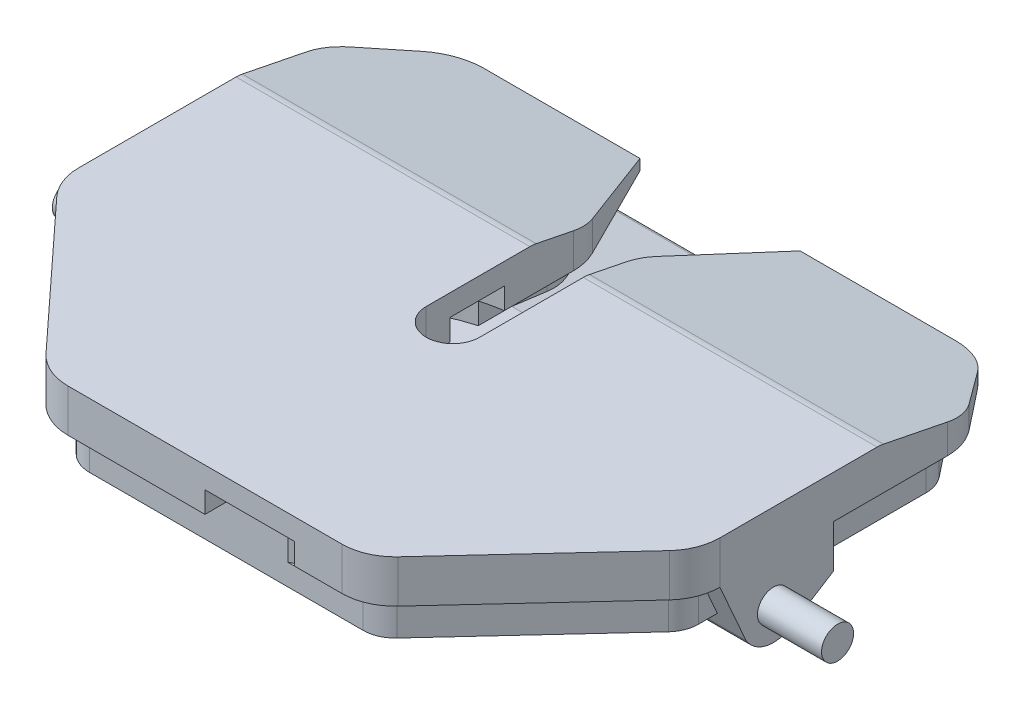
SolidWorks part; units mm, degrees
note: The reader was unsure of these and kept them because the rebuilt part matched: shared geometry of "Sketch1<4>", "Sketch4<3>".
ref_plane "Front Plane" through (0, 0, 0) normal (0, 0, 1) x (1, 0, 0)
ref_plane "Top Plane" through (0, 0, 0) normal (0, 1, 0) x (1, 0, 0)
ref_plane "Right Plane" through (0, 0, 0) normal (1, 0, 0) x (0, 0, -1)
sketch "Sketch1" plane through (0, 0, 0) normal (0, 1, 0) x (1, 0, 0)
  line L0 (-25, 0) -> (-25, 137.7264)
  line L1 (-30.4844, 160.9801) -> (-74.949, 250)
  line L2 (-74.949, 250) -> (-220.7208, 250)
  line L3 (0, 0) -> (0, 250.2014) construction
  line L4 (-45, 0) -> (-45, 133.0094)
  line L5 (-50.4844, 156.263) -> (-97.3051, 250)
  line L6 (-45, 145.283) -> (-92.8412, 241.063) construction
  line L7 (50.4844, 156.263) -> (97.3051, 250)
  line L8 (45, 0) -> (45, 133.0094)
  line L9 (74.949, 250) -> (220.7208, 250)
  line L10 (30.4844, 160.9801) -> (74.949, 250)
  line L11 (25, 0) -> (25, 137.7264)
  line L12 (-128.1169, -232.1298) -> (128.1169, -232.1298)
  line L13 (0, 0) -> (0, -232.1298) construction
  line L14 (-164.8474, -216.0543) -> (-286.7305, -84.0895)
  line L15 (-300, -50.1651) -> (-300, 162.9177)
  line L16 (-289.2422, 193.9023) -> (-259.963, 230.9846)
  line L17 (289.2422, 193.9023) -> (259.963, 230.9846)
  line L18 (300, -50.1651) -> (300, 162.9177)
  line L19 (164.8474, -216.0543) -> (286.7305, -84.0895)
  line L20 (-45, 0) -> (-45, 145.283) construction
  line L21 (-25, 0) -> (-25, 150) construction
  line L22 (-25, 150) -> (-74.949, 250) construction
  line L23 (244.2661, 218.5908) -> (220.7208, 250)
  line L24 (-273.5453, 181.5085) -> (-244.2661, 218.5908)
  line L25 (-280, -50.1651) -> (-280, 162.9177)
  line L26 (-150.1552, -202.4845) -> (-272.0383, -70.5197)
  line L27 (-128.1169, -212.1298) -> (128.1169, -212.1298)
  line L28 (150.1552, -202.4845) -> (272.0383, -70.5197)
  line L29 (280, -50.1651) -> (280, 162.9177)
  line L30 (273.5453, 181.5085) -> (244.2661, 218.5908)
  line L36 (-244.2661, 218.5908) -> (-220.7208, 250)
  line L38 (-87.3153, 230) -> (-220.7208, 230) construction
  line L39 (-48.3766, 152.0431) -> (-87.3153, 230) construction
  line L40 (-45, 0) -> (-45, 137.7264) construction
  line L41 (48.3766, 152.0431) -> (87.3153, 230) construction
  line L42 (45, 0) -> (45, 137.7264) construction
  line L43 (87.3153, 230) -> (220.7208, 230) construction
  arc A1 (-25, 0) -> (25, 0) centre (0, 0) ccw
  arc A2 (-220.7208, 250) -> (-259.963, 230.9846) centre (-220.7208, 200) ccw
  arc A3 (220.7208, 250) -> (259.963, 230.9846) centre (220.7208, 200) cw
  arc A4 (289.2422, 193.9023) -> (300, 162.9177) centre (250, 162.9177) cw
  arc A5 (300, -50.1651) -> (286.7305, -84.0895) centre (250, -50.1651) cw
  arc A6 (128.1169, -232.1298) -> (164.8474, -216.0543) centre (128.1169, -182.1298) ccw
  arc A7 (-128.1169, -232.1298) -> (-164.8474, -216.0543) centre (-128.1169, -182.1298) cw
  arc A8 (-286.7305, -84.0895) -> (-300, -50.1651) centre (-250, -50.1651) cw
  arc A9 (-300, 162.9177) -> (-289.2422, 193.9023) centre (-250, 162.9177) cw
  arc A10 (45, 133.0094) -> (50.4844, 156.263) centre (97.0392, 133.0094) cw
  arc A11 (25, 137.7264) -> (30.4844, 160.9801) centre (77.0392, 137.7264) cw
  arc A12 (-45, 133.0094) -> (-50.4844, 156.263) centre (-97.0392, 133.0094) ccw
  arc A13 (-25, 137.7264) -> (-30.4844, 160.9801) centre (-77.0392, 137.7264) ccw
  arc A15 (-280, 162.9177) -> (-273.5453, 181.5085) centre (-250, 162.9177) cw
  arc A16 (-272.0383, -70.5197) -> (-280, -50.1651) centre (-250, -50.1651) cw
  arc A17 (-128.1169, -212.1298) -> (-150.1552, -202.4845) centre (-128.1169, -182.1298) cw
  arc A18 (128.1169, -212.1298) -> (150.1552, -202.4845) centre (128.1169, -182.1298) ccw
  arc A19 (280, -50.1651) -> (272.0383, -70.5197) centre (250, -50.1651) cw
  arc A20 (273.5453, 181.5085) -> (280, 162.9177) centre (250, 162.9177) cw
  arc A23 (-45, 0) -> (45, 0) centre (0, 0) ccw
  arc A25 (-220.7208, 230) -> (-244.2661, 218.5908) centre (-220.7208, 200) ccw construction
  arc A26 (-45, 137.7264) -> (-48.3766, 152.0431) centre (-77.0392, 137.7264) ccw construction
  arc A27 (45, 137.7264) -> (48.3766, 152.0431) centre (77.0392, 137.7264) cw construction
  arc A28 (220.7208, 230) -> (244.2661, 218.5908) centre (220.7208, 200) cw construction
  point P29 (-244.949, 250)
  point P32 (244.949, 250)
  point P35 (300, 180.2776)
  point P38 (300, -69.7224)
  point P41 (150, -232.1298)
  point P44 (-150, -232.1298)
  point P47 (-300, -69.7224)
  point P50 (-300, 180.2776)
  point P53 (45, 145.283)
  point P56 (25, 150)
  point P63 (-25, 150)
  dimension "D1" = 50
  dimension "D3" = 50
  dimension "D12" = 52.0392
  dimension "D4" = 150
  dimension "D5" = 100
  dimension "D6" = 20
  dimension "D7" = 170
  dimension "D8" = 300
  dimension "D9" = 250
  dimension "D10" = 232.1298
  dimension "D11" = 300
  dimension "D13" = 20
extrude "Boss-Extrude1" add sketch "Sketch1" along normal blind 40
extrude "Boss-Extrude2" add sketch "Sketch1<4>" against normal blind 40 contours A23 L4 A12 L5 L2 L36 L24 A15 L25 A16 L26 A17 L27 A18 L28 A19 L29 A20 L30 L23 L9 L7 A10 L8
sketch "Sketch1<4>" plane through (0, 0, 0) normal (0, 1, 0) x (1, 0, 0) same geometry as "Sketch1"
sketch "Sketch2" plane through (0, 0, 0) normal (1, 0, 0) x (0, 0, -1)
  line L0 (100, 40) -> (250, 10)
  line L1 (-50.1651, 40) -> (162.9177, 40) construction
  line L3 (100, 40) -> (250, 40)
  line L4 (250, 40) -> (250, 10)
  dimension "D1" = 100
  dimension "D2" = 30
extrude "Cut-Extrude1" cut sketch "Sketch2" against normal mid plane 680
fillet "Fillet1" radius 30 2 edges at (-162.5, 40, -100) (162.5, 40, -100)
sketch "Sketch3" plane through (0, 0, 0) normal (1, 0, 0) x (0, 0, -1)
  line L0 (-181.9227, -20) -> (100, -20)
  line L1 (100, -20) -> (250, -40)
  line L2 (-50.1651, -40) -> (162.9177, -40) construction
  line L3 (-181.9227, -20) -> (-181.9227, -40)
  line L4 (-202.4845, -40) -> (-70.5197, -40) construction
  line L5 (-181.9227, -40) -> (-50.1651, -40)
  line L6 (250, -40) -> (250, -50)
  line L7 (250, -50) -> (-50.1651, -50)
  line L8 (-50.1651, -50) -> (-50.1651, -40)
  dimension "D1" = 100
  dimension "D2" = 20
  dimension "D3" = 10
extrude "Boss-Extrude3" add sketch "Sketch3" along normal mid plane 330
fillet "Fillet2" radius 5 1 edges at (0, -40, -250)
sketch "Sketch4" plane through (280, 0, 0) normal (1, 0, 0) x (0, 0, -1)
  line L0 (-50.1651, -40) -> (250, -40) construction
  line L1 (15.9641, -65.3997) -> (56.3763, -40)
  line L2 (-50.1651, -40) -> (162.9177, -40) construction
  line L3 (56.3763, -40) -> (56.3763, 0)
  line L4 (-50.1651, 0) -> (162.9177, 0) construction
  line L5 (56.3763, 0) -> (-50.1651, 0)
  line L6 (-50.1651, 0) -> (-25.6227, -55.6038)
  arc A0 (-28.7955, -48.4153) -> (15.9641, -65.3997) centre (0, -40) ccw
  circle A1 centre (0, -40) radius 15
  line M1 (162.9177, 0) -> (-50.1651, 0)
  line M3 (-50.1651, -40) -> (162.9177, -40)
  dimension "D1" = 30
  dimension "D2" = 60
extrude "Boss-Extrude4" add sketch "Sketch4" along normal blind 20 and the other way blind 80 contours A1 L3 L6 M3 M1 | A1 L6 A0 L1 M3
extrude "Boss-Extrude5" add sketch "Sketch4<3>" along normal blind 80 contours A1 M3 | A1 M3
sketch "Sketch4<3>" plane through (280, 0, 0) normal (1, 0, 0) x (0, 0, -1) same geometry as "Sketch4"
mirror "Mirror1" about plane through (0, 0, 0) normal (1, 0, 0) of "Boss-Extrude5", "Boss-Extrude4"
sketch "Sketch5" plane through (0, -20, 0) normal (0, 1, 0) x (1, 0, 0)
  line L0 (0, -90) -> (0, -255)
  line L2 (165, -90) -> (309.5262, -90)
  line L3 (0, -90) -> (-82.5, 52.8942)
  line L4 (309.5262, -90) -> (309.5262, -278.2479)
  line L5 (309.5262, -278.2479) -> (0, -255)
  line L6 (0, -90) -> (149.5408, -159.732)
  line L8 (0, -61.2237) -> (0, -90) construction
  line L9 (0, -90) -> (26.8772, -90) construction
  circle A0 centre (0, 0) radius 45
  arc A1 (-67.5, 26.9134) -> (0, -225) centre (0, -90) cw
  arc A2 (-82.5, 52.8942) -> (0, -255) centre (0, -90) cw
  circle A3 centre (0, -90) radius 135 construction
  circle A4 centre (0, -90) radius 165 construction
  line M4 (45, 0) -> (45, 100)
  line M6 (-45, 100) -> (-45, 0)
  dimension "D1" = 90
  dimension "D3" = 135
  dimension "D2" = 30
  dimension "D4" = 25
  dimension "D5" = 30
  dimension "D6" = 145
extrude "Cut-Extrude2" cut sketch "Sketch5" along normal blind 20 contours A2 A1 M6 M4 | A2 L3 A1 M6 | A2 A1 L6 M4 | A2 L6 A1 L0
sketch "Sketch6" plane through (0, 0, 0) normal (0, -1, 0) x (1, 0, 0)
  line L0 (0, 90) -> (149.5408, 159.732)
  line L1 (0, 90) -> (-82.5, -52.8942)
  line L2 (0, 90) -> (0, 68.0894) construction
  line L3 (0, 90) -> (19.1469, 90) construction
  line L4 (0, 90) -> (0, 255)
  line L5 (0, 90) -> (94.6401, -45.1601) construction
  circle A0 centre (0, 90) radius 165
  circle A1 centre (0, 90) radius 115
  circle A2 centre (0, 0) radius 25
  arc A5 (25, 0) -> (-25, 0) centre (0, 0) ccw construction
  arc A6 (45, -68.7451) -> (110.9473, 212.1298) centre (0, 90) ccw construction
  line M2 (-128.1169, 212.1298) -> (57.5266, 212.1298)
  arc M3 (57.5266, 212.1298) -> (45, -37.2792) centre (0, 90) cw
  line M4 (45, -37.2792) -> (45, 0)
  line M6 (-45, 0) -> (-45, -37.2792)
  arc M7 (-45, -37.2792) -> (-67.5, -26.9134) centre (0, 90) cw
  line M8 (-67.5, -26.9134) -> (-82.5, -52.8942)
  arc M9 (-82.5, -52.8942) -> (-45, -68.7451) centre (0, 90) ccw
  line M16 (-25, -137.7264) -> (-25, 0)
  line M18 (25, 0) -> (25, -137.7264)
  arc M25 (45, -68.7451) -> (110.9473, 212.1298) centre (0, 90) ccw
  line M34 (128.1169, 232.1298) -> (-128.1169, 232.1298)
  dimension "D3" = 330
  dimension "D4" = 230
  dimension "D1" = 30
  dimension "D2" = 25
  dimension "D5" = 145
  dimension "D6" = 145
extrude "Cut-Extrude3" cut sketch "Sketch6" against normal blind 20 contours A1 A0 M16 M18 | A1 A0 M6 M7 M8 M9 M16 | A1 A0 L0 M18 M25 M3 M4 | A0 L4 L0 M25 M34 M2 M3 | A1 L0 L4 M3 M2 | A1 L0 M4 M3 | A1 L1 M7 M6 | A0 L4 M34
sketch "Sketch7" plane through (0, 0, 0) normal (0, 1, 0) x (1, 0, 0)
  line L0 (300, -50.1651) -> (163.6778, -69.1532)
  line L1 (280, -50.1651) -> (300, -50.1651) construction
  line L2 (163.6778, -69.1532) -> (68.3705, -258.4995)
  line L3 (68.3705, -258.4995) -> (208.6094, -264.6865)
  line L4 (208.6094, -264.6865) -> (324.1003, -68.3787)
  line L5 (324.1003, -68.3787) -> (300, -50.1651)
  arc A0 (286.7305, -84.0895) -> (300, -50.1651) centre (250, -50.1651) ccw construction
  arc A1 (83.81, -232.1298) -> (25, 73.0951) centre (0, -90) ccw construction
extrude "Cut-Extrude4" cut sketch "Sketch7" against normal blind 10
